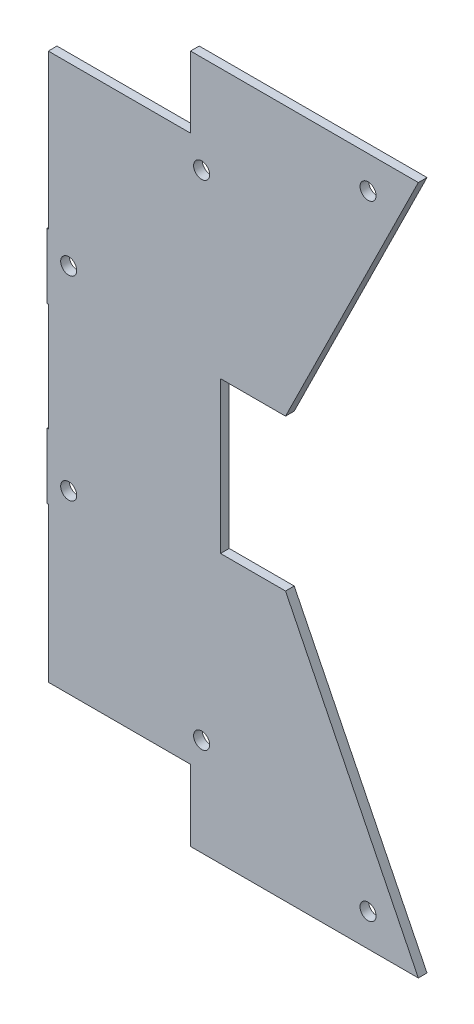
SolidWorks part; units mm, degrees
material "Thornel Mat VMA"
ref_plane "Front Plane" through (0, 0, 0) normal (0, 0, 1) x (1, 0, 0)
ref_plane "Top Plane" through (0, 0, 0) normal (0, 1, 0) x (1, 0, 0)
ref_plane "Right Plane" through (0, 0, 0) normal (1, 0, 0) x (0, 0, -1)
sketch "Sketch1" plane through (0, 0, 0) normal (0, 0, 1) x (1, 0, 0)
  line L0 (-2.9301, -104.5098) -> (-3.3149, -104.5098)
  line L1 (-3.3149, -72.8868) -> (-2.9301, -72.8868)
  line L78 (47.4851, -66.5368) -> (47.4851, -72.8868)
  line L79 (47.4851, -104.5098) -> (47.4851, -110.8598)
  line L80 (66.5174, -66.5368) -> (105.3971, 12.1397)
  line L81 (105.3971, 12.1397) -> (38.7094, 12.1397)
  line L88 (38.7094, 12.1397) -> (38.7094, -8.6883)
  line L89 (-2.9301, -8.6883) -> (38.7094, -8.6883)
  line L90 (-3.3149, -53.8368) -> (-2.9301, -53.8368)
  line L91 (-2.9301, -53.8368) -> (-2.9301, -8.6883)
  line L92 (-3.3149, -66.5368) -> (-3.3149, -53.8368)
  line L93 (-3.3149, -72.8868) -> (-3.3149, -66.5368)
  line L94 (-2.9301, -104.5098) -> (-2.9301, -72.8868)
  line L95 (-3.3149, -110.8598) -> (-3.3149, -104.5098)
  line L96 (66.5174, -110.8598) -> (105.3971, -189.5363)
  line L97 (105.3971, -189.5363) -> (38.7094, -189.5363)
  line L98 (38.7094, -189.5363) -> (38.7094, -168.7083)
  line L99 (-2.9301, -168.7083) -> (38.7094, -168.7083)
  line L106 (-3.3149, -110.8598) -> (-3.3149, -123.5598)
  line L107 (-3.3149, -123.5598) -> (-2.9301, -123.5598)
  line L108 (66.5174, -110.8598) -> (47.4851, -110.8598)
  line L109 (47.4851, -66.5368) -> (66.5174, -66.5368)
  line L110 (47.4851, -104.5098) -> (47.4851, -72.8868)
  line L111 (-2.9301, -123.5598) -> (-2.9301, -168.7083)
  circle A0 centre (90.6739, 2.6147) radius 2.3495
  circle A1 centre (41.9566, -16.4353) radius 2.3495
  circle A2 centre (3.0351, -60.1868) radius 2.3495
  circle A3 centre (3.0351, -117.2098) radius 2.3495
  circle A4 centre (41.9566, -160.9613) radius 2.3495
  circle A5 centre (90.6739, -180.0113) radius 2.3495
  point P2 (90.6739, 2.6147)
  point P4 (41.9566, -16.4353)
  point P6 (3.0351, -60.1868)
  point P8 (3.0351, -117.2098)
  point P10 (41.9566, -160.9613)
  point P11 (90.6739, -180.0113)
  dimension "D2" = 4.699
  dimension "D1" = 66.6876
extrude "Boss-Extrude1" add sketch "Sketch1" along normal blind 2.54
